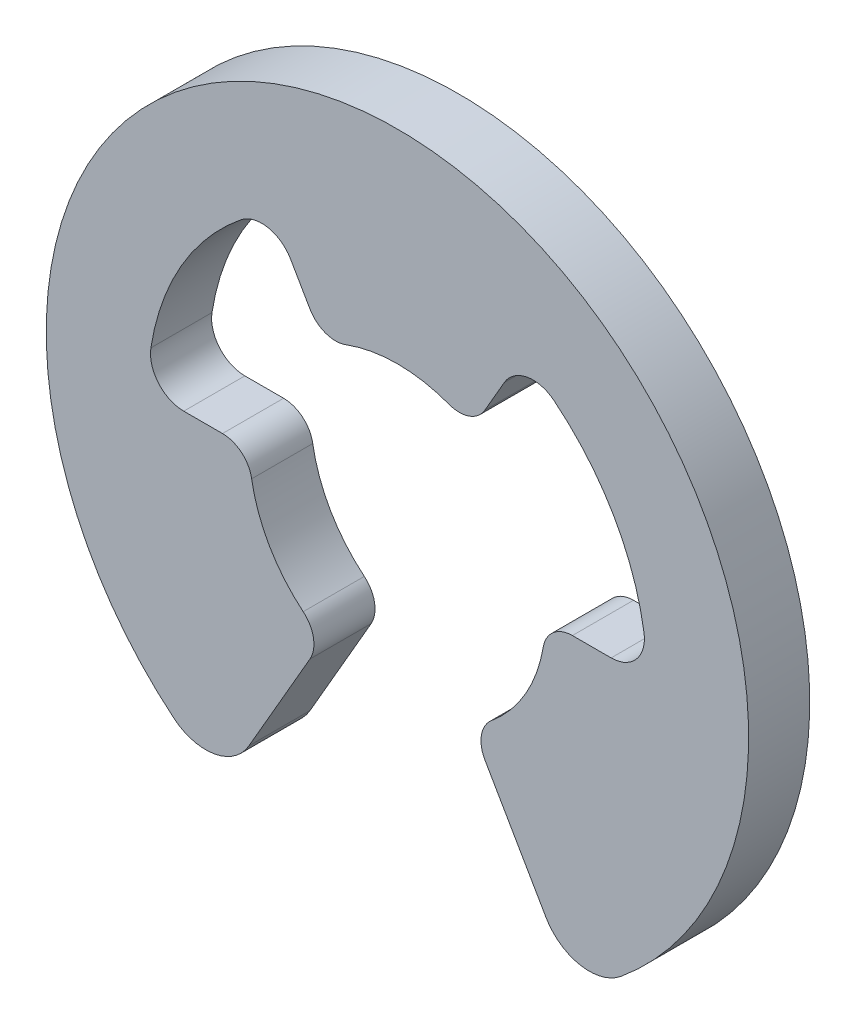
SolidWorks part; units mm, degrees
material "Plain Carbon Steel"
ref_plane "Front Plane" through (0, 0, 0) normal (0, 0, 1) x (1, 0, 0)
ref_plane "Top Plane" through (0, 0, 0) normal (0, 1, 0) x (1, 0, 0)
ref_plane "Right Plane" through (0, 0, 0) normal (1, 0, 0) x (0, 0, -1)
sketch "Sketch1" plane through (0, 0, 0) normal (0, 0, 1) x (1, 0, 0)
  line L0 (-2.6862, -4.6526) -> (-1.5816, -2.7394)
  line L1 (-3.1632, 0) -> (-3.8636, 0)
  line L2 (-1.9318, 3.3459) -> (-1.5816, 2.7394)
  line L3 (1.5816, 2.7394) -> (1.9318, 3.3459)
  line L4 (3.8636, 0) -> (3.1632, 0)
  line L5 (1.5816, -2.7394) -> (2.6862, -4.6526)
  arc A0 (4.042, -4.8974) -> (-4.042, -4.8974) centre (0, 0) ccw
  arc A1 (-4.042, -4.8974) -> (-2.6862, -4.6526) centre (-3.4677, -4.2015) ccw
  arc A2 (-1.5816, -2.7394) -> (-1.7038, -2.06) centre (-2.0446, -2.472) ccw
  arc A3 (-1.7038, -2.06) -> (-2.636, -0.4456) centre (0, 0) cw
  arc A4 (-2.636, -0.4456) -> (-3.1632, 0) centre (-3.1632, -0.5347) ccw
  arc A5 (-3.8636, 0) -> (-4.458, 0.6941) centre (-3.8636, 0.6016) cw
  arc A6 (-4.458, 0.6941) -> (-2.8301, 3.5137) centre (0, 0) cw
  arc A7 (-2.8301, 3.5137) -> (-1.9318, 3.3459) centre (-2.4527, 3.0452) cw
  arc A8 (-1.5816, 2.7394) -> (-0.9321, 2.5056) centre (-1.1185, 3.0067) ccw
  arc A9 (-0.9321, 2.5056) -> (0.9321, 2.5056) centre (0, 0) cw
  arc A10 (0.9321, 2.5056) -> (1.5816, 2.7394) centre (1.1185, 3.0067) ccw
  arc A11 (1.9318, 3.3459) -> (2.8301, 3.5137) centre (2.4527, 3.0452) cw
  arc A12 (2.8301, 3.5137) -> (4.458, 0.6941) centre (0, 0) cw
  arc A13 (4.458, 0.6941) -> (3.8636, 0) centre (3.8636, 0.6016) cw
  arc A14 (3.1632, 0) -> (2.636, -0.4456) centre (3.1632, -0.5347) ccw
  arc A15 (2.636, -0.4456) -> (1.7038, -2.06) centre (0, 0) cw
  arc A16 (1.7038, -2.06) -> (1.5816, -2.7394) centre (2.0446, -2.472) ccw
  arc A17 (2.6862, -4.6526) -> (4.042, -4.8974) centre (3.4677, -4.2015) ccw
extrude "Boss-Extrude1" add sketch "Sketch1" against normal blind 0.5524 and the other way blind 0.5524
ref_plane "RR XY" through (0, 0, 0) normal (0, 0, 1) x (1, 0, 0)
ref_plane "RR XZ" through (0, 0, 0) normal (0, -1, 0) x (-1, 0, 0)
ref_plane "RR YZ" through (0, 0, 0) normal (1, 0, 0) x (0, 0, -1)
ref_axis "RR X" through (-80.9, 0, 0) along (1, 0, 0)
ref_axis "RR Y" through (0, -50, 0) along (0, 1, 0)
ref_axis "RR Z" through (0, 0, 80.9) along (0, 0, -1)
sketch3d "RR"
  point P0 (0, 0, 0)
